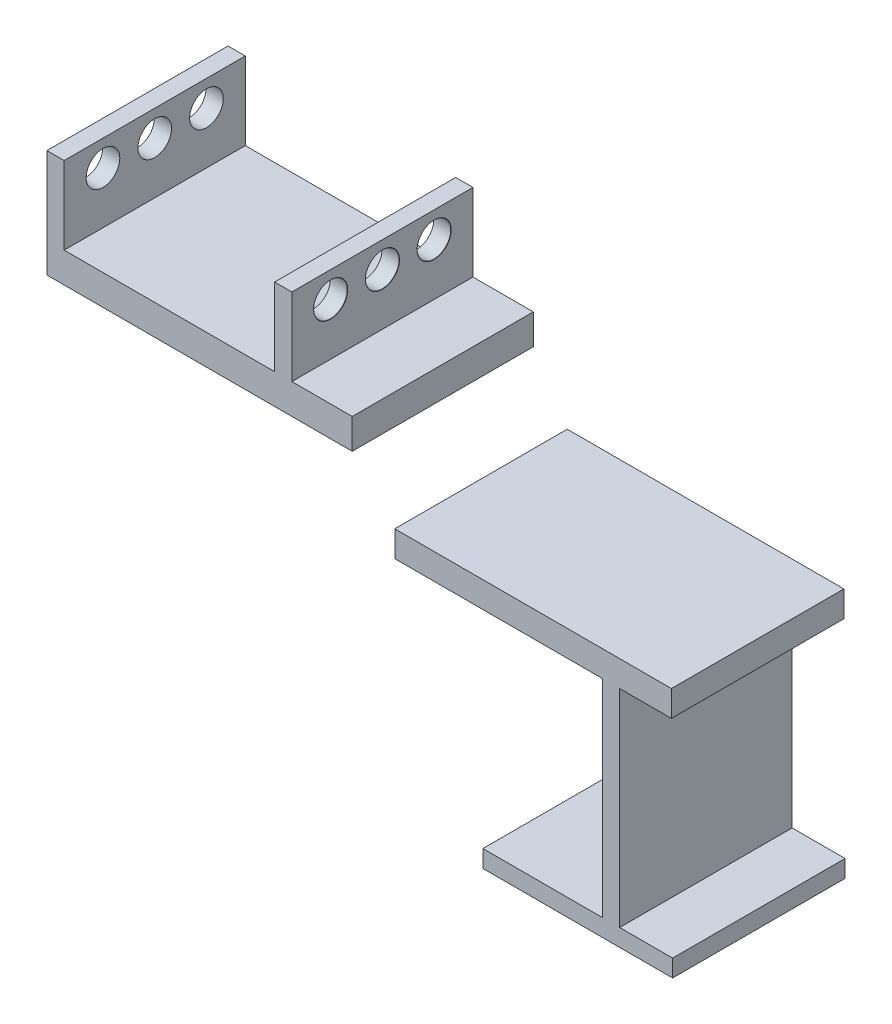
SolidWorks part; units mm, degrees
ref_plane "Front Plane" through (0, 0, 0) normal (0, 0, 1) x (1, 0, 0)
ref_plane "Top Plane" through (0, 0, 0) normal (0, 1, 0) x (1, 0, 0)
ref_plane "Right Plane" through (0, 0, 0) normal (1, 0, 0) x (0, 0, -1)
sketch "Sketch1" plane through (0, 0, 0) normal (0, 0, 1) x (1, 0, 0)
  line L0 (14.421, -30) -> (21.421, -30)
  line L2 (12.421, -21) -> (14.421, -21)
  line L3 (12.421, -21) -> (12.421, -30)
  line L5 (14.421, -21) -> (14.421, -30)
  line L6 (21.421, -33.5) -> (14.421, -33.5)
  line L7 (12.421, -30) -> (-11.979, -30)
  line L12 (-13.979, -33.5) -> (-13.979, -21)
  line L13 (-13.979, -21) -> (-11.979, -21)
  line L14 (-11.979, -30) -> (-11.979, -21)
  line L15 (-11.779, -25.9259) -> (-11.779, -23.0615) construction
  line L16 (14.421, -33.5) -> (-13.979, -33.5)
  line L20 (12.221, -23.0615) -> (12.221, -25.9259) construction
  line L21 (-11.479, -27) -> (-8.779, -27) construction
  line L30 (21.421, -33.5) -> (21.421, -30)
  dimension "D1" = 3.5
  dimension "D2" = 2
  dimension "D3" = 2
  dimension "D4" = 0.2
  dimension "D5" = 9
  dimension "D6" = 0.2
  dimension "D7" = 3
extrude "Boss-Extrude1" add sketch "Sketch1" against normal blind 21
hole_wizard "M3.5 Clearance Hole1" positions "Sketch2" profile "Sketch3" hole size "M3.5" standard "ANSI Metric" end condition through all
sketch "Sketch2" plane through (14.421, 0, 0) normal (1, 0, 0) x (0, 0, -1)
  arc A0 (2.5, -24) -> (6.5, -24) centre (4.5, -24) ccw construction
  arc A1 (2.5, -24) -> (6.5, -24) centre (4.5, -24) ccw construction
  arc A2 (8, -24) -> (13, -24) centre (10.5, -24) ccw construction
  arc A3 (8, -24) -> (13, -24) centre (10.5, -24) ccw construction
  arc A4 (8, -24) -> (13, -24) centre (10.5, -24) ccw construction
  arc A5 (8, -24) -> (13, -24) centre (10.5, -24) ccw construction
  arc A6 (14, -24) -> (19, -24) centre (16.5, -24) ccw construction
  arc A7 (14, -24) -> (19, -24) centre (16.5, -24) ccw construction
  point P0 (4.5, -24)
  point P2 (10.5, -24)
  point P4 (16.5, -24)
sketch "Sketch3" plane through (14.421, -24, -4.5) normal (0, 1, 0) x (0, 0, -1)
  line L0 (0, 0) -> (0, 28.4)
  line L1 (0, 28.4) -> (1.95, 28.4)
  line L2 (1.95, 28.4) -> (1.95, 0.025)
  line L3 (1.95, 0.025) -> (1.975, 0)
  line L5 (1.975, 0) -> (0, 0)
  line L6 (-1.95, 0.025) -> (-1.975, 0) construction
  line L11 (0, -6.35) -> (0, 107.95) construction
  dimension "Thru Hole Dia." = 3.9
  dimension "Thru Hole Depth" = 28.4
  dimension "Near C'Sink Dia." = 3.95
  dimension "Near C'Sink Angle" = 90
sketch "Sketch8" plane through (0, 0, 0) normal (0, 0, 1) x (1, 0, 0)
  line L0 (32.0241, -45.4137) -> (3.9012, -45.4137) construction
  line L1 (78.5706, -47.8137) -> (56.5706, -47.8137)
  line L3 (70.4318, -45.8137) -> (56.5706, -45.8137)
  line L4 (56.5706, -47.8137) -> (56.5706, -45.8137)
  line L8 (72.4318, -45.8137) -> (72.4318, -21.8137)
  line L10 (70.4318, -45.8137) -> (70.4318, -21.8137)
  line L11 (78.4318, -18.8137) -> (46.354, -18.8137)
  line L13 (70.4318, -21.8137) -> (46.354, -21.8137)
  line L14 (46.354, -18.8137) -> (46.354, -21.8137)
  line L15 (78.5706, -47.8137) -> (78.5706, -45.8137)
  line L16 (78.5706, -45.8137) -> (72.4318, -45.8137)
  line L18 (72.4318, -21.8137) -> (78.4318, -21.8137)
  line L19 (78.4318, -21.8137) -> (78.4318, -18.8137)
  point P17 (30.3885, -19.0311)
  dimension "D1" = 3
  dimension "D2" = 0.4
  dimension "D3" = 2
  dimension "D4" = 22
  dimension "D5" = 2
  dimension "D6" = 6
  dimension "D7" = 24
extrude "Boss-Extrude2" add sketch "Sketch8" along normal blind 20 contours L10 L13 L14 L11 L19 L18 L8 L16 L15 L1 L4 L3
sketch "Sketch9" plane through (0, -21.8137, 0) normal (0, -1, 0) x (1, 0, 0)
  circle A7 centre (8.3885, 10) radius 9.1
  point P0 (8.3885, 10)
  dimension "D1" = 18.2
sketch "Sketch10" plane through (0, -47.8137, 0) normal (0, -1, 0) x (1, 0, 0)
  point P6 (26.9626, 10)
extrude "Cut-Extrude3" cut sketch "Sketch10" against normal blind 10 rebuild error yes
sketch "Sketch13" plane through (0, -45.4137, 0) normal (0, -1, 0) x (1, 0, 0)
  line L0 (12.2626, -0.5) -> (23.6626, -0.5) construction
  line L1 (-30.5266, -0.5) -> (-12.7451, -0.5)
  line L2 (-30.5266, -0.5) -> (-30.5266, 59.6991)
  line L3 (-30.5266, 59.6991) -> (-12.7451, 59.6991)
  line L4 (-12.7451, -0.5) -> (-12.7451, 59.6991)
  line L5 (-30.5266, 29.5995) -> (-12.7451, 29.5995) construction
  line L6 (-21.6358, 59.6991) -> (-21.6358, -0.5) construction
  circle A6 centre (-15.6115, 4) radius 1.9
  circle A7 centre (-15.6115, 10) radius 1.9
  circle A8 centre (-15.6115, 16) radius 1.9
  dimension "D1" = 3.8
